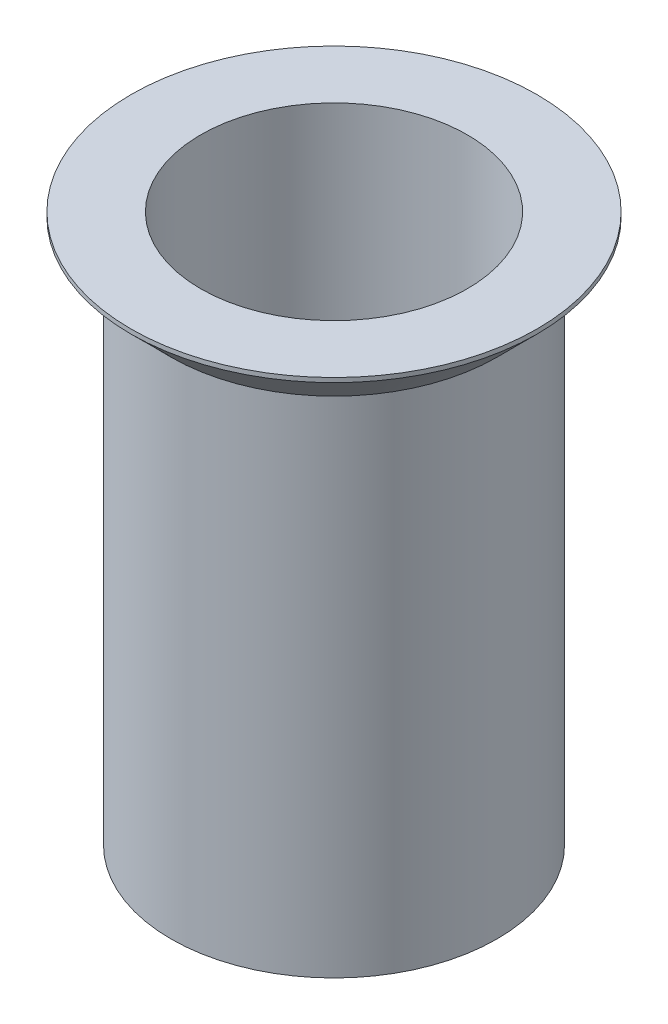
SolidWorks part; units mm, degrees
material "Handl."
ref_plane "Płaszczyzna przednia" through (0, 0, 0) normal (0, 0, 1) x (1, 0, 0)
ref_plane "Płaszczyzna górna" through (0, 0, 0) normal (0, 1, 0) x (1, 0, 0)
ref_plane "Płaszczyzna prawa" through (0, 0, 0) normal (1, 0, 0) x (0, 0, -1)
sketch "Szkic1" plane through (0, 0, 0) normal (1, 0, 0) x (0, 0, -1)
  line L0 (0, 0) -> (0, 18.5) construction
  line L1 (0, 0) -> (5.5, 0)
  line L2 (5.5, 0) -> (5.5, 17)
  line L3 (5.5, 17) -> (6.85, 18.35)
  line L4 (6.85, 18.35) -> (6.85, 18.5)
  line L5 (6.85, 18.5) -> (0, 18.5)
  line L6 (0, 0) -> (0, 18.5)
  dimension "D1" = 11
  dimension "D2" = 13.7
  dimension "D3" = 45
  dimension "D4" = 1.5
  dimension "D5" = 18.5
revolve "Obrót1" add sketch "Szkic1" angle 360 about L0
hole_wizard "Otwór pod śrubę M81" positions "Szkic2" profile "Szkic3" hole size "M8" standard "DIN"
sketch "Szkic2" plane through (0, 18.5, 0) normal (0, 1, 0) x (1, 0, 0)
  point P0 (0, 0)
sketch "Szkic3" plane through (0, 18.5, 0) normal (1, 0, 0) x (0, 0, 1)
  line L0 (0, 0) -> (0, 11.7039)
  line L1 (0, 11.7039) -> (4.5, 9)
  line L2 (4.5, 9) -> (4.5, 0)
  line L5 (4.5, 0) -> (0, 0)
  line L10 (0, 11.7039) -> (-4.5, 9) construction
  line L11 (0, -6.35) -> (0, 107.95) construction
  dimension "Średnica otworu" = 9
  dimension "Głębokość otworu" = 9
  dimension "Kąt wiertła" = 118
hole_wizard "Otwór gwintowany M81" positions "Szkic4" profile "Szkic5" tap size "M8" standard "DIN" end condition up to next
sketch "Szkic4" plane through (0, 18.5, 0) normal (0, 1, 0) x (1, 0, 0)
  point P0 (0, 0)
sketch "Szkic5" plane through (0, 18.5, 0) normal (1, 0, 0) x (0, 0, 1)
  line L0 (0, 0) -> (0, 18.5)
  line L1 (0, 18.5) -> (3.4, 18.5)
  line L2 (3.4, 18.5) -> (3.4, 0)
  line L5 (3.4, 0) -> (0, 0)
  line L11 (0, -6.35) -> (0, 107.95) construction
  dimension "Średnica otworu gwintowanego na wylot" = 6.8
  dimension "Głębokość otworu gwintowanego na wylot" = 18.5
cosmetic thread "Gwint otworu1"
